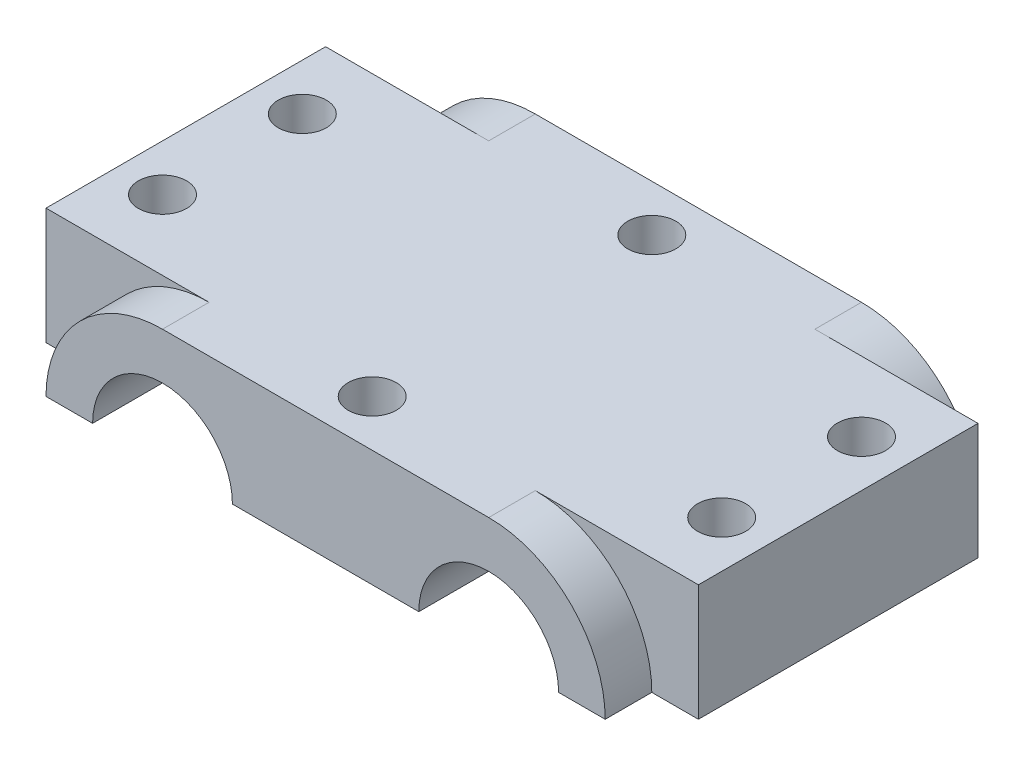
SolidWorks part; units mm, degrees
ref_plane "Front Plane" through (0, 0, 0) normal (0, 0, 1) x (1, 0, 0)
ref_plane "Top Plane" through (0, 0, 0) normal (0, 1, 0) x (1, 0, 0)
ref_plane "Right Plane" through (0, 0, 0) normal (1, 0, 0) x (0, 0, -1)
sketch "Sketch1" plane through (0, 0, 0) normal (0, 0, 1) x (1, 0, 0)
  line L0 (88.9, -15.875) -> (63.5, -15.875)
  line L1 (88.9, -15.875) -> (88.9, 15.875)
  line L2 (88.9, 15.875) -> (44.45, 15.875)
  line L3 (2.1198, -15.875) -> (2.1198, -16.8754)
  line L4 (25.4, -15.875) -> (-25.4, -15.875)
  line L6 (-88.9, -15.875) -> (-63.5, -15.875)
  line L7 (-88.9, -15.875) -> (-88.9, 15.875)
  line L8 (44.45, 15.875) -> (-44.45, 15.875)
  line L9 (-44.45, 15.875) -> (-88.9, 15.875)
  arc A0 (25.4, -15.875) -> (63.5, -15.875) centre (44.45, -15.875) cw
  arc A1 (44.45, 15.875) -> (76.2, -15.875) centre (44.45, -15.875) cw
  arc A2 (-44.45, 15.875) -> (-76.2, -15.875) centre (-44.45, -15.875) ccw
  arc A3 (-25.4, -15.875) -> (-63.5, -15.875) centre (-44.45, -15.875) ccw
  point P16 (0, -15.875)
  point P22 (0, 15.875)
  dimension "D4" = 88.9
  dimension "D5" = 31.75
  dimension "D6" = 19.05
  dimension "D1" = 88.9
  dimension "D2" = 88.9
  dimension "D3" = 31.75
extrude "Boss-Extrude9" add sketch "Sketch1" along normal mid plane 76.2 contours A2 L9 L7 L6 | L2 A1 L0 L1 region at (77.8565, 3.0668, 0) region at (-77.8565, 3.0668, 0)
extrude "Boss-Extrude10" add sketch "Sketch1<11>" along normal mid plane 101.6 contours A3 L4 A0 L0 A1 L8 A2 L6 region at (0, 1.5558, 0)
sketch "Sketch1<11>" plane through (0, 0, 0) normal (0, 0, 1) x (1, 0, 0) same geometry as "Sketch1"
sketch "Sketch3" plane through (0, 15.875, 0) normal (0, 1, 0) x (1, 0, 0)
  line L0 (0, 47.4662) -> (0, -46.8978) construction
  line L1 (-121.271, 0) -> (101.7539, 0) construction
  circle A0 centre (-76.2, 19.05) radius 6.5532
  circle A1 centre (0, 38.1) radius 6.5532
  circle A2 centre (76.2, 19.05) radius 6.5532
  circle A3 centre (76.2, -19.05) radius 6.5532
  circle A4 centre (0, -38.1) radius 6.5532
  circle A5 centre (-76.2, -19.05) radius 6.5532
  dimension "D1" = 38.1
  dimension "D5" = 13.1064
  dimension "D6" = 13.1064
  dimension "D2" = 19.05
  dimension "D3" = 152.4
  dimension "D4" = 76.2
extrude "Cut-Extrude3" cut sketch "Sketch3" against normal blind 101.6
